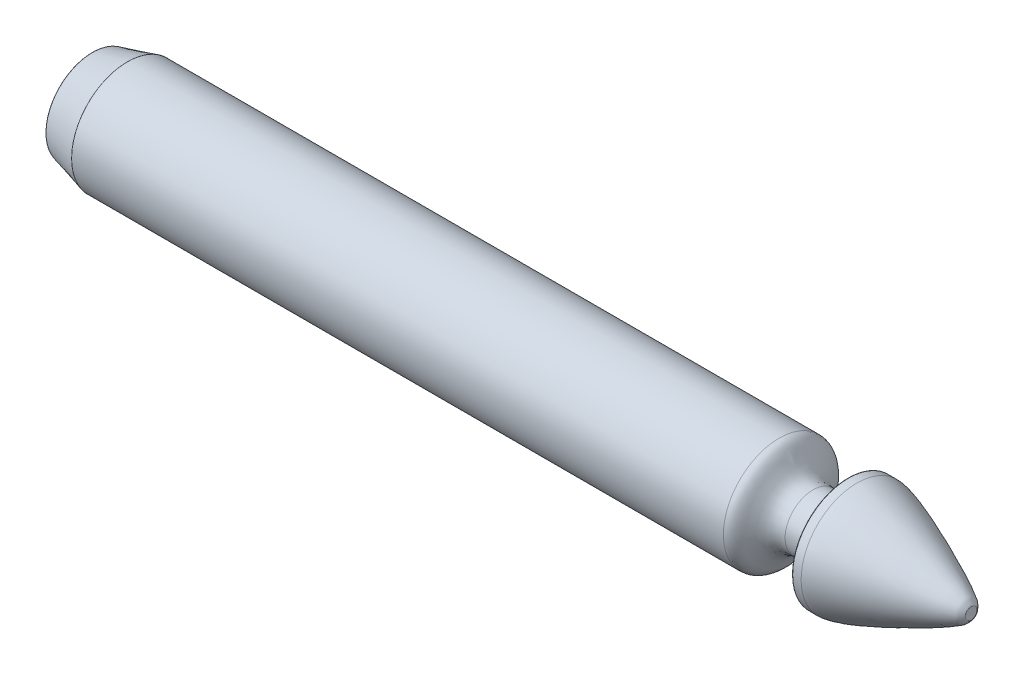
SolidWorks part; units mm, degrees
material "Stainless Steel (ferritic)"
ref_plane "Front" through (0, 0, 0) normal (0, 0, 1) x (1, 0, 0)
ref_plane "Top" through (0, 0, 0) normal (0, 1, 0) x (1, 0, 0)
ref_plane "Right" through (0, 0, 0) normal (1, 0, 0) x (0, 0, -1)
sketch "body_sketch" plane through (0, 0, 0) normal (0, 0, 1) x (1, 0, 0)
  line L1 (-16.7357, 3.175) -> (-10.9218, 3.175)
  line L2 (-48, 3.175) -> (-20.8111, 3.175)
  line L3 (-19.1074, 3.175) -> (-22.5343, 3.175) construction
  line L4 (-6.5, 3.175) -> (-7, 3.175)
  line L5 (-15.6683, 3.175) -> (-17.809, 3.175) construction
  line L6 (-50, 0) -> (-50, 2.6391)
  line L7 (-50, 2.6391) -> (-48, 3.175)
  line L9 (-7, 3.175) -> (-7, 1.5875)
  line L10 (-7, 1.5875) -> (-9, 1.5875)
  line L13 (14.3233, 1.5875) -> (12.3233, 1.5875) construction
  line L14 (-10.9218, 3.175) -> (-7, 3.175) construction
  line L15 (0, 0) -> (-50, 0)
  line L17 (0, 0.3278) -> (0, 0)
  spline S0 degree 3 poles (-6.5, 3.175) (-5.4841, 3.175) (-0.4543, 0.8964) (-0.0546, 0.4243) (0, 0.3773) (0, 0.3278) knots 0 0 0 0 0.586138 0.686138 1 1 1 1
  spline S1 degree 3 poles (-10.9218, 3.175) (-10.1654, 3.175) (-10.25, 1.5875) (-9, 1.5875) knots 0 0 0 0 1 1 1 1
  spline S2 degree 3 poles (-20.8111, 3.175) (-19.3832, 3.175) (-18.0736, 3.175) (-16.7357, 3.175) knots 0 0 0 0 1 1 1 1
  point P5 (0, 0)
  point P8 (-45.9835, 3.175)
  point P11 (-47.657, 3.175)
  dimension "D1" = 3.175
  dimension "D2" = 0.5
  dimension "D3" = 2
  dimension "D4" = 1.5875
  dimension "D5" = 50
  dimension "D6" = 7
  dimension "D7" = 3.175
  dimension "D8" = 15
  dimension "D9" = 2
revolve "body" add sketch "body_sketch" angle 360 about L15
sketch "minimum_diameter" plane through (0, 0, 0) normal (1, 0, 0) x (0, 0, -1)
  circle A0 centre (0, 0) radius 1.5875 construction
  circle A2 centre (0, 0) radius 1.5875 construction
fillet "break_edges" radius 0.02 3 edges at (-50, 2.6391, 0) (-48, 3.175, 0) (-7, 3.175, 0)
